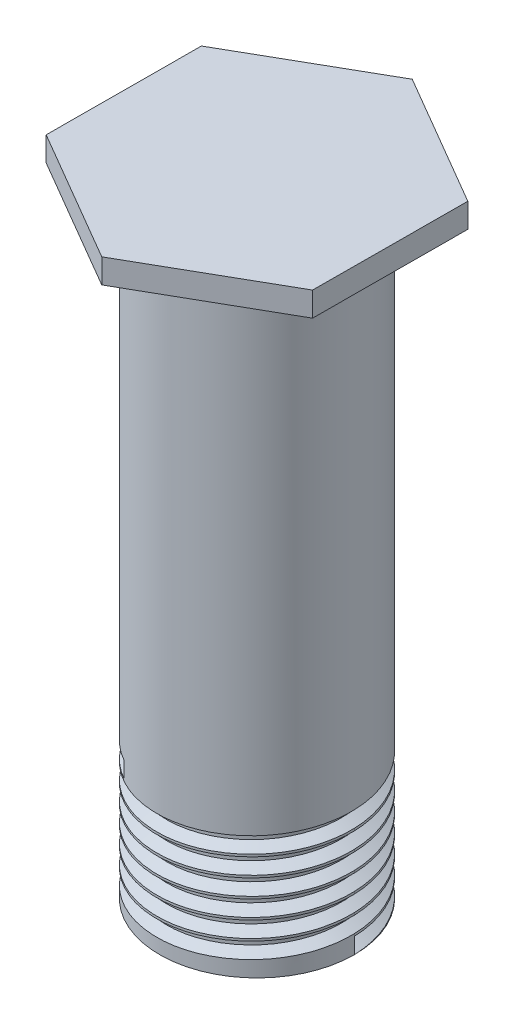
SolidWorks part; units mm, degrees
ref_plane "Front Plane" through (0, 0, 0) normal (0, 0, 1) x (1, 0, 0)
ref_plane "Top Plane" through (0, 0, 0) normal (0, 1, 0) x (1, 0, 0)
ref_plane "Right Plane" through (0, 0, 0) normal (1, 0, 0) x (0, 0, -1)
sketch "Sketch1" plane through (0, 0, 0) normal (0, 1, 0) x (1, 0, 0)
  circle A0 centre (0, 0) radius 8
extrude "Boss-Extrude1" add sketch "Sketch1" along normal blind 50
sketch "Sketch2" plane through (0, 50, 0) normal (0, 1, 0) x (1, 0, 0)
  line L1 (11.0291, 6.3002) -> (0.0584, 12.7016)
  line L2 (0.0584, 12.7016) -> (-10.9707, 6.4014)
  line L3 (-10.9707, 6.4014) -> (-11.0291, -6.3002)
  line L4 (-11.0291, -6.3002) -> (-0.0584, -12.7016)
  line L5 (-0.0584, -12.7016) -> (10.9707, -6.4014)
  line L6 (10.9707, -6.4014) -> (11.0291, 6.3002)
  circle A0 centre (0, 0) radius 11 construction
extrude "Boss-Extrude2" add sketch "Sketch2" along normal blind 2
thread "Thread1" pitch 1.5 method cut profile "Thread Profile1" start angle 0, offset 0, length 10, pitch 1.5, diameter 16
ref_plane "Plane1" through (8, 0, 0) normal (0, 0, 1) x (1, 0, 0)
sketch "Thread Profile1" plane through (8, 0, 0) normal (0, 0, 1) x (1, 0, 0)
  line L0 (0, 0) -> (0, 1.5) construction
  line L11 (0, 0) -> (0, 1.3125)
  line L12 (0, 1.3125) -> (-0.8119, 0.8437)
  line L13 (-0.8119, 0.8437) -> (-0.8119, 0.4687)
  line L15 (-0.8119, 0.4687) -> (0, 0)
  line L17 (-0.8119, 0.6562) -> (0, 0.6562) construction
  point P2 (0, 0)
  dimension "Pitch" = 1.5
  dimension "Profile_Angle" = 60
  dimension "Profile_Land" = 0.375
  dimension "Profile_Height" = 0.8119
